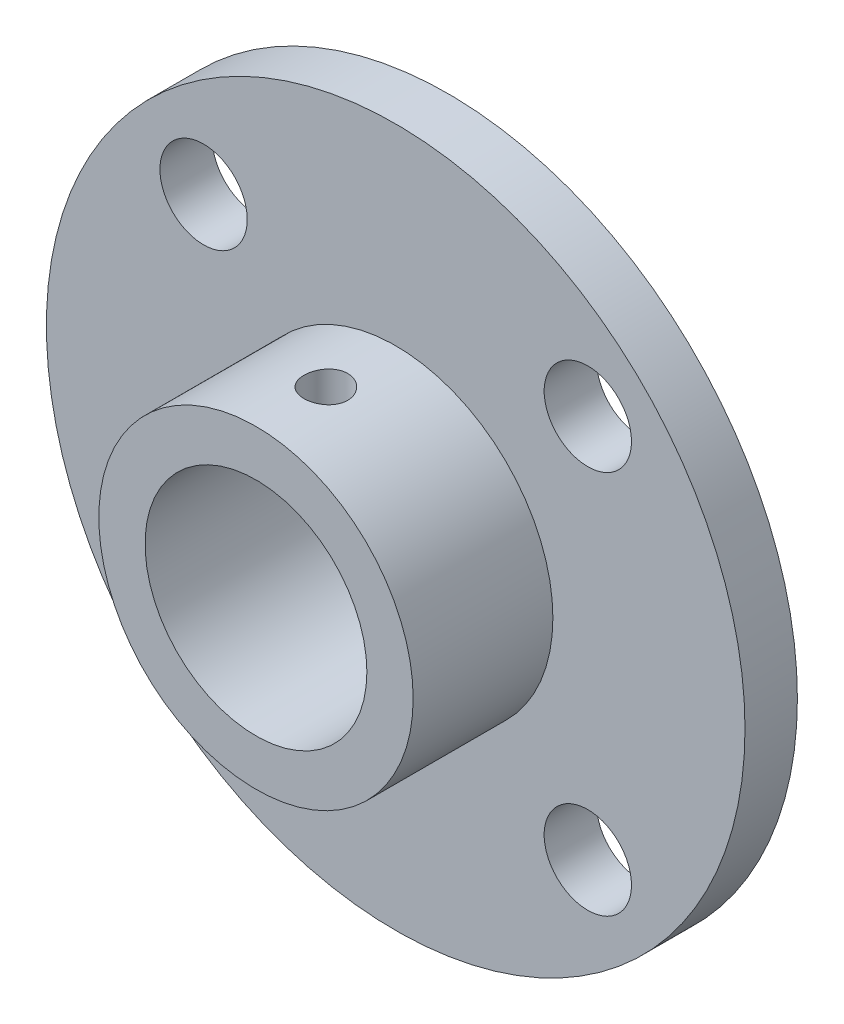
SolidWorks part; units mm, degrees
ref_plane "Front Plane" through (0, 0, 0) normal (0, 0, 1) x (1, 0, 0)
ref_plane "Top Plane" through (0, 0, 0) normal (0, 1, 0) x (1, 0, 0)
ref_plane "Right Plane" through (0, 0, 0) normal (1, 0, 0) x (0, 0, -1)
sketch "Sketch1" plane through (0, 0, 0) normal (0, 0, 1) x (1, 0, 0)
  circle A0 centre (0, 0) radius 20
  dimension "D1" = 40
extrude "Boss-Extrude1" add sketch "Sketch1" along normal blind 3
sketch "Sketch2" plane through (0, 0, 3) normal (0, 0, 1) x (1, 0, 0)
  circle A0 centre (0, 0) radius 9
  dimension "D1" = 18
extrude "Boss-Extrude2" add sketch "Sketch2" along normal blind 8
sketch "Sketch4" plane through (0, 0, 11) normal (0, 0, 1) x (1, 0, 0)
  circle A0 centre (0, 0) radius 6.35
  dimension "D1" = 12.7
extrude "Cut-Extrude1" cut sketch "Sketch4" against normal through all
ref_plane "Plane2" through (0, 0, 7) normal (0, 0, 1) x (1, 0, 0)
hole_wizard "M3 Tapped Hole1" positions "3DSketch7" profile "Sketch15" tap size "M3" standard "ISO" end condition up to next
sketch3d "3DSketch7"
  point P0 (0, 9, 7)
  dimension "D1" = 4
sketch "Sketch15" plane through (0, 9, 7) normal (1, 0, 0) x (0, 0, 1)
  line L0 (0, 0) -> (0, 2.65)
  line L1 (0, 2.65) -> (1.25, 2.65)
  line L2 (1.25, 2.65) -> (1.25, 0)
  line L5 (1.25, 0) -> (0, 0)
  line L11 (0, -6.35) -> (0, 107.95) construction
  dimension "Thru Tap Drill Dia." = 2.5
  dimension "Thru Tap Drill Depth" = 2.65
cosmetic thread "Hole Thread1" parameters "D2"=3
sketch "Sketch16" plane through (0, 0, 3) normal (0, 0, 1) x (1, 0, 0)
  line L0 (0, 0) -> (34.2865, 0) construction
  line L1 (0, 0) -> (11, 11) construction
  point P0 (11, 11)
  dimension "D1" = 11
  dimension "D2" = 45
hole_wizard "Ø5.0 (5) Diameter Hole1" positions "3DSketch8" profile "Sketch17" hole size "Ø5.0" standard "ISO" end condition through all
sketch3d "3DSketch8"
  point P0 (11, 11, 3)
sketch "Sketch17" plane through (11, 11, 3) normal (1, 0, 0) x (0, -1, 0)
  line L0 (0, 0) -> (0, 3)
  line L1 (0, 3) -> (2.5, 3)
  line L2 (2.5, 3) -> (2.5, 0)
  line L5 (2.5, 0) -> (0, 0)
  line L11 (0, -6.35) -> (0, 107.95) construction
  dimension "Thru Hole Dia." = 5
  dimension "Thru Hole Depth" = 3
sketch "Sketch18" plane through (0, 0, 0) normal (0, 0, -1) x (-1, 0, 0)
  circle A0 centre (-11, 11) radius 4.1
  dimension "D1" = 8.2
extrude "Cut-Extrude2" [suppressed] cut sketch "Sketch18" against normal offset from surface (1 mm away) 2 up to face at (13.5, 11, 3)
pattern_circular "CirPattern1" count 4 over 360 about axis through (0, 0, 11) along (0, 0, -1) of "Ø5.0 (5) Diameter Hole1", "Cut-Extrude2"
